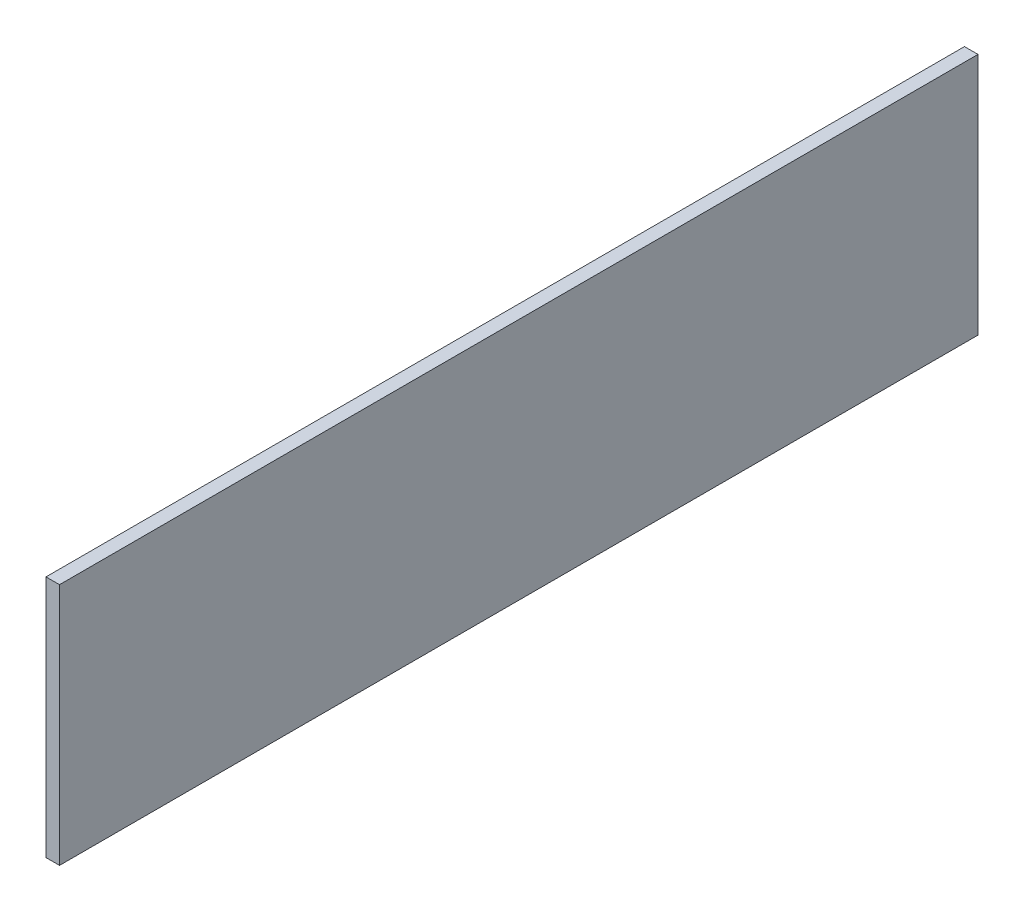
SolidWorks part; units mm, degrees
material "6061 Alloy"
ref_plane "Front" through (0, 0, 0) normal (0, 0, 1) x (1, 0, 0)
ref_plane "Top" through (0, 0, 0) normal (0, 1, 0) x (1, 0, 0)
ref_plane "Right" through (0, 0, 0) normal (1, 0, 0) x (0, 0, -1)
sketch "Sketch1" plane through (0, 0, 0) normal (1, 0, 0) x (0, 0, -1)
  line L1 (-53.975, -14.2875) -> (53.975, -14.2875)
  line L2 (-53.975, -14.2875) -> (-53.975, 14.2875)
  line L3 (-53.975, 14.2875) -> (53.975, 14.2875)
  line L4 (53.975, -14.2875) -> (53.975, 14.2875)
  line L5 (-53.975, -14.2875) -> (53.975, 14.2875) construction
  line L6 (-53.975, 14.2875) -> (53.975, -14.2875) construction
  point P0 (0, 0)
  dimension "D1" = 107.95
  dimension "D2" = 28.575
extrude "Boss-Extrude1" add sketch "Sketch1" along normal blind 1.5875 contours L2 L3 L4 L1
